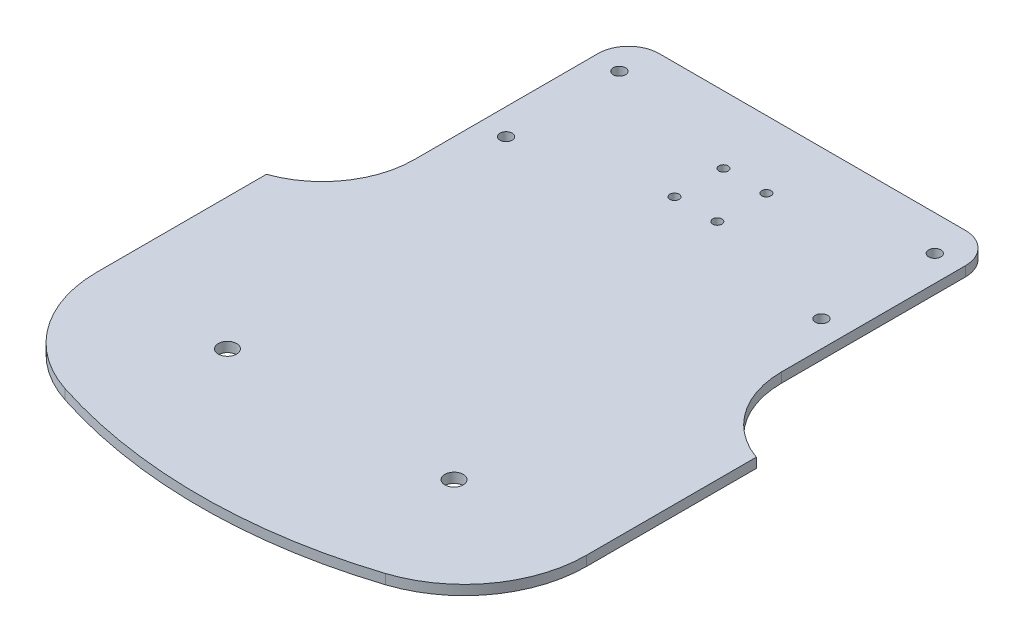
SolidWorks part; units mm, degrees
other "main"
material "Skleněné vlákno-A"
ref_plane "Přední rovina" through (0, 0, 0) normal (0, 0, 1) x (1, 0, 0)
ref_plane "Horní rovina" through (0, 0, 0) normal (0, 1, 0) x (1, 0, 0)
ref_plane "Pravá rovina" through (0, 0, 0) normal (1, 0, 0) x (0, 0, -1)
sketch "Skica1" plane through (0, 0, 0) normal (0, 1, 0) x (1, 0, 0)
  line L0 (0, 0) -> (-30, 0) construction
  line L1 (-25, 15) -> (25, 15)
  line L2 (-30, 10) -> (-30, -20)
  line L3 (0, -85) -> (-40, -85) construction
  line L4 (30, 10) -> (30, -20)
  line L5 (-40, -61.8466) -> (-40, -34.1421)
  line L6 (0, -154.3556) -> (0, 117.2396) construction
  line L7 (40, -61.8466) -> (40, -34.1421)
  arc A0 (-30, -20) -> (-40, -34.1421) centre (-45, -20) cw
  arc A1 (-25, 15) -> (-30, 10) centre (-25, 10) ccw
  arc A2 (26.1538, -80.8763) -> (-26.1538, -80.8763) centre (0, 0) cw
  arc A3 (25, 15) -> (30, 10) centre (25, 10) cw
  arc A4 (30, -20) -> (40, -34.1421) centre (45, -20) ccw
  arc A5 (40, -61.8466) -> (26.1538, -80.8763) centre (20, -61.8466) cw
  arc A6 (-26.1538, -80.8763) -> (-40, -61.8466) centre (-20, -61.8466) cw
  point P8 (32.3438, 20)
  point P13 (-30, 15)
  point P24 (0, 15)
  point P26 (40, -75)
  point P29 (-40, -75)
  dimension "D4" = 5
  dimension "D2" = 100
  dimension "D5" = 80
  dimension "D7" = 15
  dimension "D8" = 20
  dimension "D1" = 60
  dimension "D3" = 15
  dimension "D6" = 20
extrude "Přidat vysunutím1" add sketch "Skica1" along normal mid plane 1.6
sketch "Skica2" plane through (0, -0.8, 0) normal (0, -1, 0) x (1, 0, 0)
  circle A0 centre (-25.75, -9.25) radius 1 construction
  circle A1 centre (-25.75, -9.25) radius 1
  circle A2 centre (-25.75, 9.25) radius 1 construction
  circle A3 centre (25.75, 9.25) radius 1 construction
  circle A4 centre (25.75, -9.25) radius 1 construction
  circle A5 centre (-25.75, 9.25) radius 1
  circle A6 centre (25.75, 9.25) radius 1
  circle A7 centre (25.75, -9.25) radius 1
extrude "Odebrat vysunutím1" cut sketch "Skica2" against normal through all
sketch "Skica3" plane through (0, -0.8, 0) normal (0, -1, 0) x (1, 0, 0)
  line L0 (0, 0) -> (14.3407, 0) construction
  line L1 (0, 0) -> (0, 8.7788) construction
  circle A0 centre (-3.5, 4) radius 0.75
  circle A1 centre (3.5, 4) radius 0.75
  circle A2 centre (-3.5, -4) radius 0.75
  circle A3 centre (3.5, -4) radius 0.75
  dimension "D1" = 8
  dimension "D2" = 7
  dimension "D3" = 1.5
extrude "Odebrat vysunutím2" cut sketch "Skica3" against normal through all
sketch "Skica8" plane through (0, -0.8, 0) normal (0, -1, 0) x (1, 0, 0)
  circle A0 centre (18.5, 62) radius 1.5 construction
  circle A1 centre (18.5, 62) radius 1.5
  circle A2 centre (-18.5, 62) radius 1.5 construction
  circle A3 centre (-18.5, 62) radius 1.5
extrude "Odebrat vysunutím4" cut sketch "Skica8" against normal through all
sketch "Skica5" plane through (0, -0.8, 0) normal (0, -1, 0) x (1, 0, 0)
  line L0 (40, 61.8466) -> (40, 34.1421) construction
  line L2 (-40, 34.1421) -> (-40, 61.8466) construction
  arc A0 (26.1538, 80.8763) -> (-26.1538, 80.8763) centre (0, 0) ccw construction
  circle A1 centre (-22.7593, 74.6057) radius 0.25
  circle A2 centre (-30, 72) radius 0.25
  circle A3 centre (-15.2971, 76.4853) radius 0.25
  circle A4 centre (-7.6859, 77.6204) radius 0.25
  circle A5 centre (0, 78) radius 0.25
  circle A6 centre (7.6859, 77.6204) radius 0.25
  circle A7 centre (15.2971, 76.4853) radius 0.25
  circle A8 centre (22.7593, 74.6057) radius 0.25
  circle A9 centre (30, 72) radius 0.25
  arc A10 (26.1538, 80.8763) -> (-26.1538, 80.8763) centre (0, 0) ccw construction
  point P28 (0, 85)
  dimension "D1" = 7
  dimension "D4" = 0.5
  dimension "D5" = 10
  dimension "D6" = 7
  dimension "D7" = 7
  dimension "D8" = 7.6953
  dimension "D2" = 10
  dimension "D3" = 9
sketch "keepouts" plane through (0, -0.8, 0) normal (0, -1, 0) x (1, 0, 0)
  line L0 (-21.5, 7.5) -> (-21.5, 8.75) construction
  line L1 (-29.75, 7.5) -> (-18.75, 7.5) construction
  line L2 (-21.5, -8.75) -> (-21.5, -7.5) construction
  line L3 (-21.5, -7.5) -> (-18.75, -7.5) construction
  line L4 (-21.5, 7.5) -> (-21.5, 8.75)
  line L5 (-21.5, 7.5) -> (-18.75, 7.5)
  line L6 (-21.5, -8.75) -> (-21.5, -7.5)
  line L7 (-21.5, -7.5) -> (-18.75, -7.5)
  line L8 (18.5, 11) -> (18.5, 29)
  line L9 (-16.5, 9) -> (16.5, 9)
  line L10 (-18.5, 29) -> (-18.5, 11)
  line L11 (16.5, 31) -> (-16.5, 31)
  line L12 (18.5, 11) -> (18.5, 29)
  line L13 (-16.5, 9) -> (16.5, 9)
  line L14 (-18.5, 29) -> (-18.5, 11)
  line L15 (16.5, 31) -> (-16.5, 31)
  line L16 (-4.8, -2.5) -> (-4.8, 2.5) construction
  line L17 (-18.75, 7.5) -> (-4.8, 7.5)
  line L18 (21.5, 8.75) -> (21.5, 7.5) construction
  line L19 (-18.75, -7.5) -> (-4.8, -7.5)
  line L20 (-4.8, 7.5) -> (-4.8, -7.5)
  line L21 (21.5, 8.75) -> (21.5, 7.5)
  line L22 (18.75, 7.5) -> (29.75, 7.5) construction
  line L23 (18.75, 7.5) -> (21.5, 7.5)
  line L24 (29.75, -7.5) -> (18.75, -7.5) construction
  line L25 (21.5, -7.5) -> (21.5, -8.75) construction
  line L26 (21.5, -7.5) -> (18.75, -7.5)
  line L27 (21.5, -7.5) -> (21.5, -8.75)
  line L28 (4.8, 2.5) -> (4.8, -2.5) construction
  line L29 (18.75, 7.5) -> (4.8, 7.5)
  line L30 (-22.5, 57) -> (-22.5, 62) construction
  line L31 (18.75, -7.5) -> (4.8, -7.5)
  line L32 (4.8, 7.5) -> (4.8, -7.5)
  line L33 (-22.5, 55) -> (-14.5, 55) construction
  line L34 (-14.5, 55) -> (-14.5, 57) construction
  line L35 (-14.5, 57) -> (-14.5, 62) construction
  line L36 (-22.5, 57) -> (-22.5, 55) construction
  line L37 (-22.5, 57) -> (-22.5, 62)
  line L38 (-22.5, 55) -> (-14.5, 55)
  line L39 (-14.5, 55) -> (-14.5, 57)
  line L40 (-14.5, 57) -> (-14.5, 62)
  line L41 (-22.5, 57) -> (-22.5, 55)
  line L42 (22.5, 57) -> (22.5, 62) construction
  line L43 (22.5, 55) -> (22.5, 57) construction
  line L44 (14.5, 55) -> (22.5, 55) construction
  line L45 (14.5, 57) -> (14.5, 55) construction
  line L46 (14.5, 57) -> (14.5, 62) construction
  line L47 (22.5, 57) -> (22.5, 62)
  line L48 (22.5, 55) -> (22.5, 57)
  line L49 (14.5, 55) -> (22.5, 55)
  line L50 (14.5, 57) -> (14.5, 55)
  line L51 (14.5, 57) -> (14.5, 62)
  arc A0 (-21.5, 8.75) -> (-30, 8.75) centre (-25.75, 8.75) ccw construction
  arc A1 (-30, -8.75) -> (-21.5, -8.75) centre (-25.75, -8.75) ccw construction
  arc A2 (-21.5, 8.75) -> (-30, 8.75) centre (-25.75, 8.75) ccw
  arc A3 (-30, -8.75) -> (-21.5, -8.75) centre (-25.75, -8.75) ccw
  arc A4 (30, 8.75) -> (21.5, 8.75) centre (25.75, 8.75) ccw construction
  arc A5 (30, 8.75) -> (21.5, 8.75) centre (25.75, 8.75) ccw
  arc A6 (21.5, -8.75) -> (30, -8.75) centre (25.75, -8.75) ccw construction
  arc A7 (21.5, -8.75) -> (30, -8.75) centre (25.75, -8.75) ccw
  arc A8 (18.5, 29) -> (16.5, 31) centre (16.5, 29) ccw
  arc A9 (16.5, 9) -> (18.5, 11) centre (16.5, 11) ccw
  arc A10 (-18.5, 11) -> (-16.5, 9) centre (-16.5, 11) ccw
  arc A11 (-16.5, 31) -> (-18.5, 29) centre (-16.5, 29) ccw
  arc A12 (18.5, 29) -> (16.5, 31) centre (16.5, 29) ccw
  arc A13 (16.5, 9) -> (18.5, 11) centre (16.5, 11) ccw
  arc A14 (-18.5, 11) -> (-16.5, 9) centre (-16.5, 11) ccw
  arc A15 (-16.5, 31) -> (-18.5, 29) centre (-16.5, 29) ccw
  arc A16 (-14.5, 62) -> (-22.5, 62) centre (-18.5, 62) ccw construction
  arc A17 (-14.5, 62) -> (-22.5, 62) centre (-18.5, 62) ccw
  arc A18 (22.5, 62) -> (14.5, 62) centre (18.5, 62) ccw construction
  arc A19 (22.5, 62) -> (14.5, 62) centre (18.5, 62) ccw
  dimension "D1" = 1
